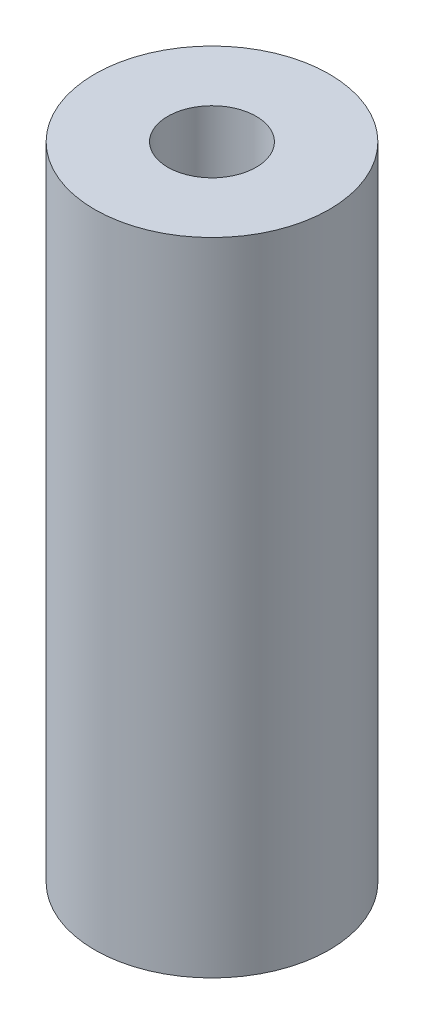
SolidWorks part; units mm, degrees
ref_plane "Front Plane" through (0, 0, 0) normal (0, 0, 1) x (1, 0, 0)
ref_plane "Top Plane" through (0, 0, 0) normal (0, 1, 0) x (1, 0, 0)
ref_plane "Right Plane" through (0, 0, 0) normal (1, 0, 0) x (0, 0, -1)
sketch "Sketch1" plane through (0, 0, 0) normal (0, 1, 0) x (1, 0, 0)
  circle A0 centre (0, 0) radius 3
  dimension "D1" = 6
extrude "Boss-Extrude1" add sketch "Sketch1" along normal blind 16.4
hole_wizard "#4-40 Tapped Hole1" positions "Sketch2" profile "Sketch3" tap size "#4-40" standard "ANSI Inch" end condition through all
sketch "Sketch2" plane through (0, 16.4, 0) normal (0, 1, 0) x (1, 0, 0)
  point P0 (0, 0)
sketch "Sketch3" plane through (0, 16.4, 0) normal (1, 0, 0) x (0, 0, 1)
  line L0 (0, 0) -> (0, 16.4)
  line L1 (0, 16.4) -> (1.1303, 16.4)
  line L2 (1.1303, 16.4) -> (1.1303, 0)
  line L5 (1.1303, 0) -> (0, 0)
  line L11 (0, -6.35) -> (0, 107.95) construction
  dimension "Thru Tap Drill Dia." = 2.2606
  dimension "Thru Tap Drill Depth" = 16.4
cosmetic thread "Hole Thread1"
